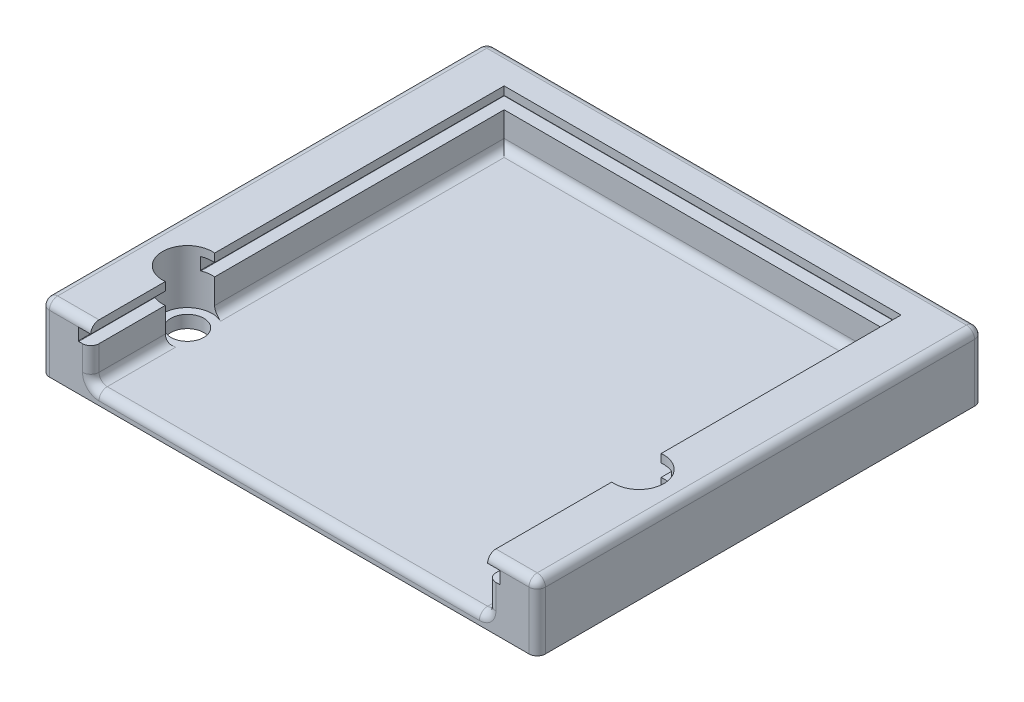
SolidWorks part; units mm, degrees
note: The reader was unsure of these and kept them because the rebuilt part matched: shared geometry of "Sketch2<7>".
ref_plane "Front Plane" through (0, 0, 0) normal (0, 0, 1) x (1, 0, 0)
ref_plane "Top Plane" through (0, 0, 0) normal (0, 1, 0) x (1, 0, 0)
ref_plane "Right Plane" through (0, 0, 0) normal (1, 0, 0) x (0, 0, -1)
sketch "Sketch2" plane through (0, 0, 0) normal (0, 1, 0) x (1, 0, 0)
  line L1 (0, 0) -> (60, 0)
  line L2 (0, 0) -> (0, 50)
  line L3 (0, 50) -> (60, 50)
  line L4 (60, 0) -> (60, 50)
  line L12 (6, 50) -> (6, 0)
  line L13 (54, 50) -> (54, 0)
  line L14 (0, 0) -> (-2, 0)
  line L15 (0, 25) -> (6, 25) construction
  line L16 (-2, 0) -> (-4, 0)
  line L17 (54, 25) -> (60, 25) construction
  line L18 (60, 0) -> (59, 0)
  line L19 (59, 0) -> (61, 0)
  line L20 (0, 50) -> (0, 53.897)
  line L21 (0, 53.897) -> (60, 53.897)
  line L22 (60, 50) -> (60, 53.897)
  line L23 (54.3156, 18) -> (60, 18) construction
  line L24 (5.6844, 12) -> (0, 12) construction
  circle A0 centre (5.6844, 12) radius 2
  circle A1 centre (54.3156, 18) radius 2
  circle A2 centre (5.6844, 12) radius 3
  circle A3 centre (54.3156, 18) radius 3
  dimension "D3" = 12
  dimension "D8" = 1
  dimension "D1" = 48
  dimension "D2" = 50
  dimension "D4" = 18
  dimension "D5" = 49
  dimension "D7" = 1
  dimension "D9" = 60
extrude "Boss-Extrude1" add sketch "Sketch2" along normal blind 1.5 contours A3 L13 L3 L12 A2 L1 | L13 A3 A1 | L13 A3 A1 | L12 A2 A0 | L12 A2 A0
extrude "Boss-Extrude4" add sketch "Sketch2<7>" along normal blind 8 contours A0 L12 L3 L2 L1 | L3 L22 L21 L20 | A3 L13 L1 L4 L3
sketch "Sketch2<7>" plane through (0, 0, 0) normal (0, 1, 0) x (1, 0, 0) same geometry as "Sketch2"
sketch "Sketch3" plane through (0, 8, 0) normal (0, 1, 0) x (1, 0, 0)
  line L0 (5, 0) -> (5, 51)
  line L1 (54, 35.4917) -> (55, 35.4917) construction
  line L2 (0, 0) -> (6, 0) construction
  line L3 (5, 51) -> (55, 51)
  line L4 (55, 51) -> (55, 0)
  line L5 (54, 0) -> (60, 0) construction
  line L6 (5, 25.5) -> (6, 25.5) construction
  line L7 (6, 50) -> (6, 14.9833) construction
  line L8 (54, 50) -> (54, 20.9833) construction
  line L10 (30, 51) -> (30, 50) construction
  line L11 (6, 50) -> (54, 50) construction
  dimension "D1" = 50
sketch "Sketch6" plane through (6, 0, 0) normal (1, 0, 0) x (0, 0, -1)
  line L0 (0, 5.5) -> (50, 5.5)
  line L1 (0, 8) -> (0, 1.5) construction
  line L2 (50, 8) -> (50, 1.5) construction
  line L3 (0, 7) -> (50, 7)
  line L4 (0, 7) -> (0, 5.5)
  line L5 (50, 7) -> (50, 5.5)
  line L8 (9.0167, 1.5) -> (0, 1.5) construction
  dimension "D1" = 1.5
  dimension "D2" = 4
extrude "Cut-Extrude1" cut sketch "Sketch6" against normal blind 1.5
sketch "Sketch10" plane through (54, 0, 0) normal (-1, 0, 0) x (0, 0, 1)
  line L0 (-50, 8) -> (-50, 1.5) construction
  line L1 (-50, 5.5) -> (0, 5.5)
  line L2 (-50, 5.5) -> (-50, 7)
  line L3 (-50, 7) -> (0, 7)
  line L4 (0, 5.5) -> (0, 7)
  line L5 (0, 8) -> (0, 1.5) construction
  line L7 (-15.0167, 1.5) -> (0, 1.5) construction
  dimension "D1" = 1.5
  dimension "D2" = 4
extrude "Cut-Extrude2" cut sketch "Sketch10" against normal blind 1.5
sketch "Sketch11" plane through (0, 0, -50) normal (0, 0, 1) x (1, 0, 0)
  line L1 (4.5, 5.5) -> (55.5, 5.5)
  line L2 (4.5, 5.5) -> (4.5, 7)
  line L3 (4.5, 7) -> (55.5, 7)
  line L4 (55.5, 5.5) -> (55.5, 7)
extrude "Cut-Extrude3" cut sketch "Sketch11" against normal blind 1.5
fillet "Fillet1" radius 1 17 edges at (6, 1.5, -4.5083) (6, 1.5, -32.4917) (30, 1.5, -50) (54, 1.5, -35.4917) (54, 1.5, -7.5083) (30, 1.5, 0) (54, 3.5, 0) (6, 3.5, 0) (60, 4, -53.897) (0, 4, -53.897) (30, 8, -53.897) (0, 4, 0) (60, 4, 0) (60, 8, -26.9485) (57, 8, 0) (3, 8, 0) (0, 8, -26.9485)
fillet "Fillet2" radius 0.05 6 edges at (4.5, 7, -4.6218) (4.5, 5.5, -4.6218) (30, 7, -51.5) (30, 5.5, -51.5) (55.5, 5.5, -7.6218) (55.5, 7, -7.6218)
